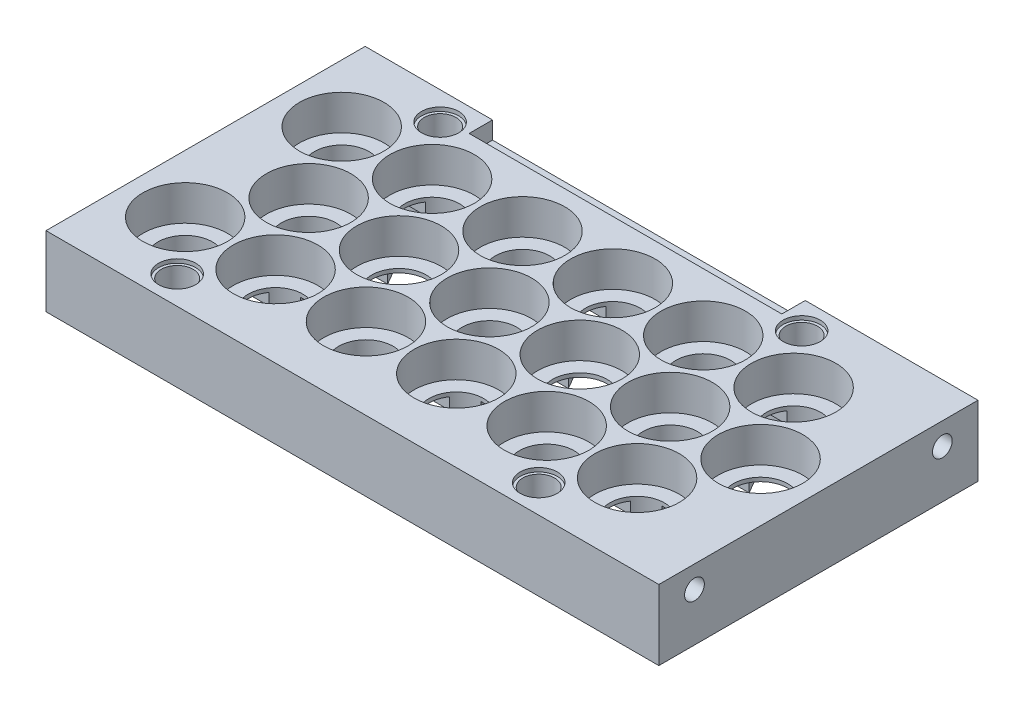
SolidWorks part; units mm, degrees
ref_plane "Front Plane" through (0, 0, 0) normal (0, 0, 1) x (1, 0, 0)
ref_plane "Top Plane" through (0, 0, 0) normal (0, 1, 0) x (1, 0, 0)
ref_plane "Right Plane" through (0, 0, 0) normal (1, 0, 0) x (0, 0, -1)
sketch "Sketch1" plane through (0, 0, 0) normal (0, 1, 0) x (1, 0, 0)
  line L0 (0, 0) -> (11.575, -20.0485) construction
  line L1 (11.575, -20.0485) -> (0, -40.097) construction
  line L2 (0, 0) -> (11.575, 0) construction
  line L3 (11.575, 0) -> (11.575, -20.0485) construction
  line L4 (11.575, -20.0485) -> (11.575, -40.097) construction
  line L5 (11.575, -40.097) -> (0, -40.097) construction
  line L6 (0, 0) -> (23.15, 0) construction
  line L7 (0, 0) -> (23.15, 0) construction
  line L8 (-14.825, -60.922) -> (142.15, -60.922)
  line L9 (-14.825, -60.922) -> (-14.825, 20.825)
  line L10 (-14.825, 20.825) -> (142.15, 20.825)
  line L11 (142.15, -60.922) -> (142.15, 20.825)
  circle A0 centre (0, 0) radius 10.825
  circle A1 centre (11.575, -20.0485) radius 10.825
  circle A2 centre (0, -40.097) radius 10.825
  circle A3 centre (23.15, 0) radius 10.825
  circle A4 centre (34.725, -20.0485) radius 10.825
  circle A5 centre (23.15, -40.097) radius 10.825
  circle A6 centre (46.3, 0) radius 10.825
  circle A7 centre (57.875, -20.0485) radius 10.825
  circle A8 centre (46.3, -40.097) radius 10.825
  circle A9 centre (69.45, 0) radius 10.825
  circle A10 centre (81.025, -20.0485) radius 10.825
  circle A11 centre (69.45, -40.097) radius 10.825
  circle A12 centre (92.6, 0) radius 10.825
  circle A13 centre (104.175, -20.0485) radius 10.825
  circle A14 centre (92.6, -40.097) radius 10.825
  circle A15 centre (115.75, 0) radius 10.825
  circle A16 centre (127.325, -20.0485) radius 10.825
  circle A17 centre (115.75, -40.097) radius 10.825
  circle A18 centre (0, 0) radius 7
  circle A19 centre (11.575, -20.0485) radius 7
  circle A20 centre (0, -40.097) radius 7
  circle A21 centre (23.15, 0) radius 7
  circle A22 centre (34.725, -20.0485) radius 7
  circle A23 centre (23.15, -40.097) radius 7
  circle A24 centre (46.3, 0) radius 7
  circle A25 centre (57.875, -20.0485) radius 7
  circle A26 centre (46.3, -40.097) radius 7
  circle A27 centre (69.45, 0) radius 7
  circle A28 centre (81.025, -20.0485) radius 7
  circle A29 centre (69.45, -40.097) radius 7
  circle A30 centre (92.6, 0) radius 7
  circle A31 centre (104.175, -20.0485) radius 7
  circle A32 centre (92.6, -40.097) radius 7
  circle A33 centre (115.75, 0) radius 7
  circle A34 centre (127.325, -20.0485) radius 7
  circle A35 centre (115.75, -40.097) radius 7
  dimension "D3" = 21.65
  dimension "D11" = 14
  dimension "D1" = 60
  dimension "D2" = 60
  dimension "D4" = 1.5
  dimension "D6" = 23.15
  dimension "D7" = 4
  dimension "D8" = 4
  dimension "D9" = 10
  dimension "D10" = 10
  dimension "D13" = 23.15
  dimension "D5" = 6
  dimension "D12" = 6
extrude "Boss-Extrude2" add sketch "Sketch1" along normal blind 11 and the other way blind 2 contours L8 L11 L10 L9 A17 A16 A15 A14 A13 A12 A11 A10 A9 A8 A7 A6 A5 A4 A3 A2 A1 A0 region at (-13.0551, 0, 20.0485)
extrude "Boss-Extrude3" add sketch "Sketch1<3>" along normal blind 2 and the other way up to surface (2 mm away) contours A0 A18 | A3 A21 | A6 A24 | A9 A27 | A12 A30 | A15 A33 | A1 A19 | A4 A22 | A7 A25 | A10 A28 | A13 A31 | A16 A34 | A17 A35 | A14 A32 | A11 A29 | A8 A26 | A5 A23 | A2 A20 region at (-10.5188, 0, 0) region at (1.0562, 0, 20.0485) region at (-10.5188, 0, 40.097) region at (12.6312, 0, 0) region at (24.2062, 0, 20.0485) region at (12.6312, 0, 40.097) region at (35.7812, 0, 0) region at (47.3562, 0, 20.0485) region at (35.7812, 0, 40.097) region at (58.9312, 0, 0) region at (70.5062, 0, 20.0485) region at (58.9312, 0, 40.097) region at (82.0812, 0, 0) region at (93.6562, 0, 20.0485) region at (82.0812, 0, 40.097) region at (105.2312, 0, 0) region at (116.8062, 0, 20.0485) region at (105.2312, 0, 40.097) other way up to face at (115.75, -2, 50.922)
sketch "Sketch1<3>" plane through (0, 0, 0) normal (0, 1, 0) x (1, 0, 0) same geometry as "Sketch1"
sketch "Sketch2" plane through (0, -2, 0) normal (0, -1, 0) x (1, 0, 0)
  line L0 (0, 40.097) -> (11.575, 20.0485) construction
  line L1 (3.4641, 42.097) -> (15.0391, 22.0485)
  line L2 (-3.4641, 38.097) -> (8.1109, 18.0485)
  line L3 (11.575, 20.0485) -> (0, 0) construction
  line L4 (15.0391, 18.0485) -> (3.4641, -2)
  line L5 (8.1109, 22.0485) -> (-3.4641, 2)
  line L6 (19.6859, 38.097) -> (31.2609, 18.0485)
  line L7 (26.6141, 42.097) -> (38.1891, 22.0485)
  line L8 (31.2609, 22.0485) -> (19.6859, 2)
  line L9 (38.1891, 18.0485) -> (26.6141, -2)
  line L10 (23.15, 40.097) -> (34.725, 20.0485) construction
  line L11 (34.725, 20.0485) -> (23.15, 0) construction
  line L12 (42.8359, 38.097) -> (54.4109, 18.0485)
  line L13 (49.7641, 42.097) -> (61.3391, 22.0485)
  line L14 (54.4109, 22.0485) -> (42.8359, 2)
  line L15 (61.3391, 18.0485) -> (49.7641, -2)
  line L16 (46.3, 40.097) -> (57.875, 20.0485) construction
  line L17 (57.875, 20.0485) -> (46.3, 0) construction
  line L18 (65.9859, 38.097) -> (77.5609, 18.0485)
  line L19 (72.9141, 42.097) -> (84.4891, 22.0485)
  line L20 (77.5609, 22.0485) -> (65.9859, 2)
  line L21 (84.4891, 18.0485) -> (72.9141, -2)
  line L22 (69.45, 40.097) -> (81.025, 20.0485) construction
  line L23 (81.025, 20.0485) -> (69.45, 0) construction
  line L24 (89.1359, 38.097) -> (100.7109, 18.0485)
  line L25 (96.0641, 42.097) -> (107.6391, 22.0485)
  line L26 (100.7109, 22.0485) -> (89.1359, 2)
  line L27 (107.6391, 18.0485) -> (96.0641, -2)
  line L28 (92.6, 40.097) -> (104.175, 20.0485) construction
  line L29 (104.175, 20.0485) -> (92.6, 0) construction
  line L30 (112.2859, 38.097) -> (123.8609, 18.0485)
  line L31 (119.2141, 42.097) -> (130.7891, 22.0485)
  line L32 (123.8609, 22.0485) -> (112.2859, 2)
  line L33 (130.7891, 18.0485) -> (119.2141, -2)
  line L34 (115.75, 40.097) -> (127.325, 20.0485) construction
  line L35 (127.325, 20.0485) -> (115.75, 0) construction
  line L36 (-3.4641, 38.097) -> (19.6859, 38.097) construction
  line L37 (0, 40.097) -> (115.75, 40.097) construction
  line L38 (0, 44.097) -> (115.75, 44.097)
  line L39 (0, 36.097) -> (115.75, 36.097)
  line L40 (11.575, 20.0485) -> (127.325, 20.0485) construction
  line L41 (11.575, 24.0485) -> (127.325, 24.0485)
  line L42 (11.575, 16.0485) -> (127.325, 16.0485)
  line L43 (0, 0) -> (115.75, 0) construction
  line L44 (0, 4) -> (115.75, 4)
  line L45 (0, -4) -> (115.75, -4)
  arc A0 (3.4641, 42.097) -> (-3.4641, 38.097) centre (0, 40.097) ccw
  arc A1 (8.1109, 18.0485) -> (15.0391, 22.0485) centre (11.575, 20.0485) ccw
  arc A2 (15.0391, 18.0485) -> (8.1109, 22.0485) centre (11.575, 20.0485) ccw
  arc A3 (-3.4641, 2) -> (3.4641, -2) centre (0, 0) ccw
  arc A4 (26.6141, 42.097) -> (19.6859, 38.097) centre (23.15, 40.097) ccw
  arc A5 (31.2609, 18.0485) -> (38.1891, 22.0485) centre (34.725, 20.0485) ccw
  arc A6 (38.1891, 18.0485) -> (31.2609, 22.0485) centre (34.725, 20.0485) ccw
  arc A7 (19.6859, 2) -> (26.6141, -2) centre (23.15, 0) ccw
  arc A8 (49.7641, 42.097) -> (42.8359, 38.097) centre (46.3, 40.097) ccw
  arc A9 (54.4109, 18.0485) -> (61.3391, 22.0485) centre (57.875, 20.0485) ccw
  arc A10 (61.3391, 18.0485) -> (54.4109, 22.0485) centre (57.875, 20.0485) ccw
  arc A11 (42.8359, 2) -> (49.7641, -2) centre (46.3, 0) ccw
  arc A12 (72.9141, 42.097) -> (65.9859, 38.097) centre (69.45, 40.097) ccw
  arc A13 (77.5609, 18.0485) -> (84.4891, 22.0485) centre (81.025, 20.0485) ccw
  arc A14 (84.4891, 18.0485) -> (77.5609, 22.0485) centre (81.025, 20.0485) ccw
  arc A15 (65.9859, 2) -> (72.9141, -2) centre (69.45, 0) ccw
  arc A16 (96.0641, 42.097) -> (89.1359, 38.097) centre (92.6, 40.097) ccw
  arc A17 (100.7109, 18.0485) -> (107.6391, 22.0485) centre (104.175, 20.0485) ccw
  arc A18 (107.6391, 18.0485) -> (100.7109, 22.0485) centre (104.175, 20.0485) ccw
  arc A19 (89.1359, 2) -> (96.0641, -2) centre (92.6, 0) ccw
  arc A20 (119.2141, 42.097) -> (112.2859, 38.097) centre (115.75, 40.097) ccw
  arc A21 (123.8609, 18.0485) -> (130.7891, 22.0485) centre (127.325, 20.0485) ccw
  arc A22 (130.7891, 18.0485) -> (123.8609, 22.0485) centre (127.325, 20.0485) ccw
  arc A23 (112.2859, 2) -> (119.2141, -2) centre (115.75, 0) ccw
  arc A24 (0, 44.097) -> (0, 36.097) centre (0, 40.097) ccw
  arc A25 (115.75, 36.097) -> (115.75, 44.097) centre (115.75, 40.097) ccw
  arc A26 (11.575, 24.0485) -> (11.575, 16.0485) centre (11.575, 20.0485) ccw
  arc A27 (127.325, 16.0485) -> (127.325, 24.0485) centre (127.325, 20.0485) ccw
  arc A28 (0, 4) -> (0, -4) centre (0, 0) ccw
  arc A29 (115.75, -4) -> (115.75, 4) centre (115.75, 0) ccw
  point P3 (5.7875, 30.0727)
  point P8 (5.7875, 10.0242)
  point P18 (28.9375, 30.0727)
  point P25 (28.9375, 10.0242)
  point P34 (52.0875, 30.0727)
  point P39 (52.0875, 10.0242)
  point P48 (75.2375, 30.0727)
  point P53 (75.2375, 10.0242)
  point P62 (98.3875, 30.0727)
  point P67 (98.3875, 10.0242)
  point P76 (121.5375, 30.0727)
  point P81 (121.5375, 10.0242)
  point P91 (57.875, 40.097)
  point P96 (69.45, 20.0485)
  point P103 (57.875, 0)
  circle M99 centre (0, 0) radius 7
  circle M100 centre (23.15, 0) radius 7
  circle M101 centre (46.3, 0) radius 7
  circle M102 centre (69.45, 0) radius 7
  circle M103 centre (92.6, 0) radius 7
  circle M104 centre (115.75, 0) radius 7
  circle M105 centre (11.575, 20.0485) radius 7
  circle M106 centre (34.725, 20.0485) radius 7
  circle M107 centre (57.875, 20.0485) radius 7
  circle M108 centre (81.025, 20.0485) radius 7
  circle M109 centre (104.175, 20.0485) radius 7
  circle M110 centre (127.325, 20.0485) radius 7
  circle M111 centre (115.75, 40.097) radius 7
  circle M112 centre (92.6, 40.097) radius 7
  circle M113 centre (69.45, 40.097) radius 7
  circle M114 centre (46.3, 40.097) radius 7
  circle M115 centre (23.15, 40.097) radius 7
  circle M116 centre (0, 40.097) radius 7
  dimension "D1" = 8
  dimension "D3" = 23.15
  dimension "D4" = 8
  dimension "D5" = 8
  dimension "D6" = 8
extrude "Cut-Extrude1" cut sketch "Sketch2" against normal blind 3 contours L1 L39 L38 M115 M116 | L6 L41 L7 L39 M106 M115 | L42 L8 L6 L41 M105 M106 | L45 L44 L4 M99 M100 | L44 L9 L42 L8 M100 M106 | L8 L42 M106 | L41 L6 M106 | L39 L1 M116 | L44 L4 M99 | L44 L9 M100 | L42 L20 L18 L41 M107 M108 | L45 L44 L15 M101 M102 | L13 L39 L38 M113 M114 | L18 L41 L19 L39 M108 M113 | L44 L21 L42 L20 M102 M108 | L45 L44 L27 M103 M104 | L42 L32 L30 L41 M109 M110 | L25 L39 L38 M111 M112 | L30 L41 L31 M110 M111 | L42 L32 L33 M104 M110 | L32 L42 M110 | L41 L30 M110 | L44 L27 M103 | L39 L25 M112 | L44 L21 M102 | L39 L19 M113 | L44 L15 M101 | L20 L42 M108 | L41 L18 M108 | L39 L13 M114 | L39 L7 M115 region at (11.6138, -2, 40.1242) region at (6.3461, -2, 36.4331) region at (23.0718, -2, 20.0485) region at (28.9375, -2, 30.0727) region at (28.3789, -2, 23.7124) region at (29.4961, -2, 36.4331) region at (57.9138, -2, 40.1242) region at (28.3789, -2, 16.3846) region at (28.9375, -2, 10.0242) region at (6.3461, -2, 3.6639) region at (11.6138, -2, -0.0272) region at (52.6461, -2, 36.4331) region at (29.4961, -2, 3.6639) region at (75.2375, -2, 30.0727) region at (75.7961, -2, 36.4331) region at (104.2138, -2, 40.1242) region at (74.6789, -2, 23.7124) region at (69.3718, -2, 20.0485) region at (57.9138, -2, -0.0272) region at (98.9461, -2, 36.4331) region at (74.6789, -2, 16.3846) region at (52.6461, -2, 3.6639) region at (121.5416, -2, 30.12) region at (75.2375, -2, 10.0242) region at (120.9789, -2, 23.7124) region at (115.6718, -2, 20.0485) region at (75.7961, -2, 3.6639) region at (104.2138, -2, -0.0272) region at (121.5416, -2, 9.977) region at (120.9789, -2, 16.3846) region at (98.9461, -2, 3.6639)
sketch "Sketch9" plane through (0, 11, 0) normal (0, 1, 0) x (1, 0, 0)
  line L0 (11.575, -60.922) -> (11.575, 20.825)
  line L1 (-14.825, 20.825) -> (142.15, 20.825) construction
  line L2 (104.175, 20.825) -> (104.175, -60.922)
  line L3 (-14.825, -60.922) -> (142.15, -60.922) construction
  circle A0 centre (11.575, 13.625) radius 4.0767
  circle A1 centre (11.575, -53.722) radius 4.0767
  circle A2 centre (104.175, -53.722) radius 4.0767
  circle A3 centre (104.175, 13.625) radius 4.0767
  point P0 (11.575, 13.625)
  point P7 (11.575, -20.0485)
  point P15 (104.175, -20.0485)
  point P20 (104.175, 13.625)
  point P21 (104.175, -53.722)
  point P22 (11.575, -53.722)
  dimension "D5" = 8.1534
  dimension "D1" = 7.2
  dimension "D4" = 7.2
extrude "Cut-Extrude3" cut sketch "Sketch9" against normal up to next contours A2 | A1 | A0 | A3
sketch "Sketch10" plane through (0, 11, 0) normal (0, 1, 0) x (1, 0, 0)
  circle A0 centre (11.575, 13.625) radius 4.7625
  circle A1 centre (104.175, 13.625) radius 4.7625
  circle A2 centre (104.175, -53.722) radius 4.7625
  circle A3 centre (11.575, -53.722) radius 4.7625
  dimension "D1" = 9.525
extrude "Cut-Extrude4" cut sketch "Sketch10" against normal blind 1
sketch "Sketch13" plane through (0, -2, 0) normal (0, -1, 0) x (1, 0, 0)
  line L0 (142.15, 60.922) -> (142.15, -20.825) construction
  line L5 (3.575, 53.722) -> (3.575, 60.922)
  line L8 (-14.825, 60.922) -> (142.15, 60.922) construction
  line L9 (3.575, 60.922) -> (19.575, 60.922)
  line L10 (19.575, 60.922) -> (19.575, 53.722)
  line L12 (57.875, 20.0485) -> (57.875, -20.825) construction
  line L13 (-14.825, -20.825) -> (142.15, -20.825) construction
  line L14 (11.575, 20.0485) -> (127.325, 20.0485) construction
  line L16 (96.175, 60.922) -> (96.175, 53.722)
  line L17 (112.175, 60.922) -> (96.175, 60.922)
  line L18 (112.175, 53.722) -> (112.175, 60.922)
  line L19 (-14.825, 60.922) -> (142.15, 60.922)
  line L20 (-14.825, 60.922) -> (-14.825, 53.922)
  line L21 (-14.825, 53.922) -> (142.15, 53.922)
  line L22 (142.15, 60.922) -> (142.15, 53.922)
  line L23 (142.15, -20.825) -> (142.15, -13.825)
  line L24 (-14.825, -13.825) -> (142.15, -13.825)
  line L25 (-14.825, -20.825) -> (-14.825, -13.825)
  line L26 (-14.825, -20.825) -> (142.15, -20.825)
  line L27 (112.175, -13.625) -> (112.175, -20.825)
  line L28 (112.175, -20.825) -> (96.175, -20.825)
  line L29 (96.175, -20.825) -> (96.175, -13.625)
  line L32 (19.575, -20.825) -> (19.575, -13.625)
  line L33 (3.575, -20.825) -> (19.575, -20.825)
  line L34 (3.575, -13.625) -> (3.575, -20.825)
  line L36 (-14.825, 53.922) -> (-9.825, 53.922)
  line L37 (-14.825, 53.922) -> (-14.825, -13.825)
  line L38 (-14.825, -13.825) -> (-9.825, -13.825)
  line L39 (-9.825, 53.922) -> (-9.825, -13.825)
  line L40 (142.15, 53.922) -> (137.15, 53.922)
  line L41 (142.15, 53.922) -> (142.15, -13.825)
  line L42 (142.15, -13.825) -> (137.15, -13.825)
  line L43 (137.15, 53.922) -> (137.15, -13.825)
  circle A4 centre (11.575, 53.722) radius 4.0767
  circle A5 centre (11.575, 53.722) radius 8
  circle A6 centre (104.175, 53.722) radius 8
  circle A7 centre (104.175, 53.722) radius 4.0767
  circle A8 centre (104.175, -13.625) radius 4.0767
  circle A9 centre (104.175, -13.625) radius 8
  circle A10 centre (11.575, -13.625) radius 8
  circle A11 centre (11.575, -13.625) radius 4.0767
  circle A12 centre (11.575, 53.722) radius 4.0767 construction
  dimension "D2" = 16
  dimension "D3" = 7
  dimension "D1" = 5
  dimension "D4" = 5
extrude "Boss-Extrude7" add sketch "Sketch13" along normal blind 5 contours L21 L5 | A5 L5 L21 | A5 L21 L10 | L10 L21 L16 | L21 A5 L19 A4 | A5 L21 A4 | L21 A6 L16 | L21 A7 A6 L19 | L21 A7 A6 | A6 L21 L18 | L18 L21 | A9 L24 L29 L26 | L28 A9 L24 A8 | A9 L26 L27 L24 | L24 L27 L26 | L32 L26 L29 L24 | L24 A9 A8 | L34 L24 | L26 A10 L24 L34 | L24 A11 A10 | L24 A11 A10 L33 | L24 A10 L26 L32 | L39 L21 L37 L24 | L21 L43 L24 L41 region at (3.7554, -2, 53.8197) region at (-5.625, -2, 57.422) region at (4.8234, -2, 59.2386) region at (4.9969, -2, 57.9605) region at (-12.325, -2, 20.0485) region at (18.3266, -2, 59.2386) region at (57.875, -2, 57.422) region at (-5.625, -2, -17.325) region at (97.4234, -2, 59.2386) region at (4.8234, -2, -19.1416) region at (96.3554, -2, 53.8197) region at (97.5969, -2, 57.9605) region at (3.7554, -2, -13.7228) region at (5.5404, -2, -13.9996) region at (110.9266, -2, 59.2386) region at (127.1625, -2, 57.422) region at (18.3266, -2, -19.1416) region at (57.875, -2, -17.325) region at (139.65, -2, 20.0485) region at (97.4234, -2, -19.1416) region at (127.1625, -2, -17.325) region at (96.3554, -2, -13.7228) region at (98.1404, -2, -13.9996) region at (110.9266, -2, -19.1416)
sketch "Sketch18" plane through (0, 0, -20.825) normal (0, 0, -1) x (-1, 0, 0)
  line L1 (-97.9, 11) -> (-17.8, 11)
  line L2 (-97.9, 11) -> (-17.8, 11)
  line L3 (-97.9, 11) -> (-97.9, 6.525)
  line L4 (-17.8, 11) -> (-17.8, 6.525)
  line L5 (-97.9, 6.525) -> (-17.8, 6.525)
  line L6 (-104.15, 11) -> (-11.55, 11)
  line L7 (14.825, 11) -> (-142.15, 11) construction
  point P7 (-57.85, 11)
  point P10 (-57.85, 11)
  line M8 (14.825, 11) -> (-142.15, 11)
  dimension "D1" = 80.1
  dimension "D2" = 4.475
  dimension "D3" = 92.6
  dimension "D4" = 38
extrude "Cut-Extrude6" cut sketch "Sketch18" against normal blind 6 contours L3 L5 L4 M8 region at (57.85, 8.7625, -20.825)
sketch "Sketch19" plane through (0, 0, -20.825) normal (0, 0, -1) x (-1, 0, 0)
  line L0 (-85.9, 6.525) -> (-29.8, 6.525)
  line L1 (-85.9, 6.525) -> (-85.9, -0.2375)
  line L2 (-29.8, 6.525) -> (-29.8, -0.2375)
  line L3 (-85.9, -0.2375) -> (-29.8, -0.2375)
  line L4 (-97.9, 6.525) -> (-17.8, 6.525) construction
  line L5 (-97.9, 6.525) -> (-17.8, 6.525) construction
  line L6 (-85.9, 6.525) -> (-97.9, 6.525) construction
  line L7 (-29.8, 6.525) -> (-17.8, 6.525) construction
  line L8 (-57.85, 6.525) -> (-57.85, -7)
  line L9 (14.825, -7) -> (-142.15, -7) construction
  circle A0 centre (-85.9, -0.2375) radius 1.9431
  circle A1 centre (-29.8, -0.2375) radius 1.9431
  point P17 (-57.85, -0.2375)
  dimension "D2" = 3.8862
  dimension "D1" = 12
extrude "Cut-Extrude7" cut sketch "Sketch19" against normal blind 5 contours L1 A0 L3 | L3 A0 L1 | L3 A1 L2 | L2 A1 L3 region at (85.0753, 0.5872, -20.825) region at (86.1749, -0.5124, -20.825) region at (29.5251, -0.5124, -20.825) region at (30.6247, 0.5872, -20.825)
sketch "Sketch20" plane through (142.15, 0, 0) normal (1, 0, 0) x (0, 0, -1)
  circle A0 centre (-51.7985, 5.325) radius 2.5273
  circle A1 centre (11.7015, 5.325) radius 2.5273
  circle A2 centre (-51.7985, 5.325) radius 2.525 construction
  circle A3 centre (11.7015, 5.325) radius 2.525 construction
  dimension "D1" = 5.0546
extrude "Cut-Extrude8" cut sketch "Sketch20" against normal blind 10 contours A0 | A0 | A1 region at (142.15, 5.325, 51.7985)
sketch "Sketch21" plane through (0, -2, 0) normal (0, -1, 0) x (1, 0, 0)
  line L0 (57.875, 44.097) -> (57.875, 53.922) construction
  line L1 (52.0446, 44.097) -> (63.7054, 44.097) construction
  line L2 (19.5725, 53.922) -> (96.1775, 53.922) construction
  line L3 (121.4946, 44.097) -> (137.15, 44.097) construction
  line L4 (137.15, 53.922) -> (137.15, -13.825) construction
  line L5 (57.875, 20.0485) -> (-2.625, 20.0485) construction
  line L6 (4.575, 20.0485) -> (-9.825, 20.0485) construction
  line L7 (-9.825, 53.922) -> (-9.825, -13.825) construction
  line L8 (121.4946, -4) -> (137.15, -4) construction
  line L9 (57.875, -4) -> (57.875, -13.825) construction
  circle A0 centre (57.875, 49.0095) radius 1.9431
  circle A1 centre (129.3223, 44.097) radius 1.9431
  arc A2 (122.0864, 37.122) -> (110.0054, 44.097) centre (115.75, 40.097) ccw construction
  circle A3 centre (-2.625, 20.0485) radius 1.9431
  arc A4 (17.3196, 24.0485) -> (17.3196, 16.0485) centre (11.575, 20.0485) ccw construction
  circle A5 centre (129.3223, -4) radius 1.9431
  circle A6 centre (57.875, -8.9125) radius 1.9431
  dimension "D1" = 3.8862
extrude "Cut-Extrude9" cut sketch "Sketch21" against normal blind 3.81
equation "\"hole_diameter\"= 21.65"
equation "\"D3@Sketch1\"=\"hole_diameter\""
equation "\"cell_spacing\"= 1.5"
equation "\"D4@Sketch1\"=\"cell_spacing\""
equation "\"D6@Sketch1\"=\"hole_diameter\"+\"cell_spacing\""
equation "\"len_spacing\"= 4"
equation "\"D7@Sketch1\"=\"len_spacing\""
equation "\"D8@Sketch1\"=\"len_spacing\""
equation "\"wid_spacing\"= 10"
equation "\"D9@Sketch1\"=\"wid_spacing\""
equation "\"D10@Sketch1\"=\"wid_spacing\""
equation "\"nipple\"= 14"
equation "\"D11@Sketch1\"=\"nipple\""
equation "\"D13@Sketch1\"=\"hole_diameter\"+\"cell_spacing\""
equation "\"channel\"= 8"
equation "\"D1@Sketch2\"=\"channel\""
equation "\"D3@Sketch2\"=\"hole_diameter\"+\"cell_spacing\""
equation "\"D4@Sketch2\"=\"channel\""
equation "\"D5@Sketch2\"=\"channel\""
equation "\"D6@Sketch2\"=\"channel\""
equation "\"lip\"= 7"
equation "\"lip_height\"= 1"
equation "\"outer_fillet\"=6"
equation "\"insert_placement\"= 7.2"
equation "\"D4@Sketch9\"=\"insert_placement\""
equation "\"D1@Sketch9\"=\"insert_placement\""
equation "\"heat_insert_diameter\"=8.1534"
equation "\"D5@Sketch9\"=\"heat_insert_diameter\""
equation "\"heat_insert_lip_diameter\"=9.525"
equation "\"D1@Sketch10\"=\"heat_insert_lip_diameter\""
equation "\"bolt_head_diameter\"=13"
equation "\"D2@Sketch13\"=\"bolt_head_diameter\"+3"
equation "\"D3@Sketch13\"=\"lip\""
equation "\"small_heat_insert\"= .153in"
equation "\"bdm_cut_depth\"=6"
equation "\"D1@Cut-Extrude6\"=\"bdm_cut_depth\""
equation "\"D2@Sketch19\"=\"small_heat_insert\""
equation "\"heat_insert_depth\"=3.81"
equation "\"D1@Sketch21\"=\"small_heat_insert\""
equation "\"heat_insert_space\"=6"
equation "\"heat_insert\"=5.5"
